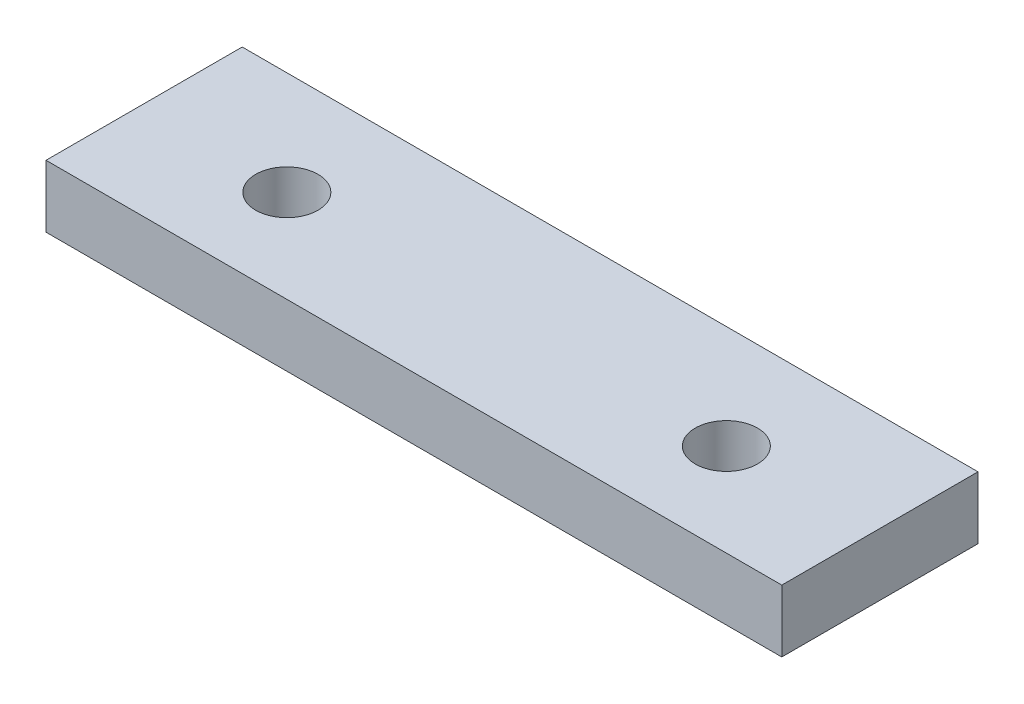
SolidWorks part; units mm, degrees
ref_plane "Front Plane" through (0, 0, 0) normal (0, 0, 1) x (1, 0, 0)
ref_plane "Top Plane" through (0, 0, 0) normal (0, 1, 0) x (1, 0, 0)
ref_plane "Right Plane" through (0, 0, 0) normal (1, 0, 0) x (0, 0, -1)
sketch "Sketch1" plane through (0, 0, 0) normal (1, 0, 0) x (0, 0, -1)
  line L1 (0, 0) -> (40, 0)
  line L2 (0, 0) -> (0, 12.7)
  line L3 (0, 12.7) -> (40, 12.7)
  line L4 (40, 0) -> (40, 12.7)
  dimension "D1" = 12.7
  dimension "D2" = 40
extrude "Boss-Extrude1" add sketch "Sketch1" along normal blind 150
sketch "Sketch2" plane through (0, 12.7, 0) normal (0, 1, 0) x (1, 0, 0)
  line L0 (0, 18.9) -> (30.2, 18.9) construction
  line L2 (150, 18.9) -> (119.8, 18.9) construction
  line L5 (150, 0) -> (0, 0) construction
  line L6 (0, 40) -> (0, 0) construction
  line L7 (150, 40) -> (150, 0) construction
  circle A0 centre (30.2, 18.9) radius 6.35
  circle A1 centre (119.8, 18.9) radius 6.35
  point P2 (10.1563, 20)
  point P3 (0, 0)
  point P10 (0, 0)
  point P11 (0, 0)
  point P14 (0, 0)
  dimension "D2" = 12.7
  dimension "D4" = 12.7
  dimension "D1" = 30.2
  dimension "D3" = 30.2
  dimension "D5" = 18.9
extrude "Cut-Extrude1" cut sketch "Sketch2" against normal up to next
